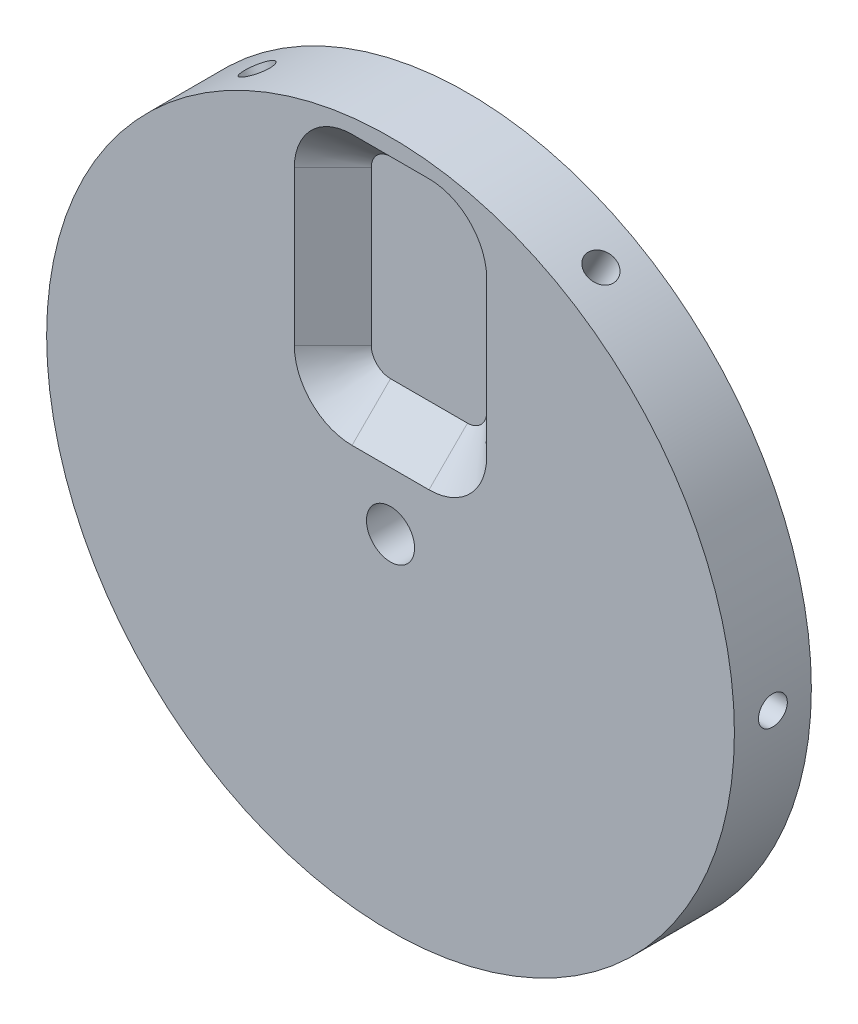
SolidWorks part; units mm, degrees
material "ABS"
ref_plane "Front Plane" through (0, 0, 0) normal (0, 0, 1) x (1, 0, 0)
ref_plane "Top Plane" through (0, 0, 0) normal (0, 1, 0) x (1, 0, 0)
ref_plane "Right Plane" through (0, 0, 0) normal (1, 0, 0) x (0, 0, -1)
sketch "Sketch1" plane through (0, 0, 0) normal (0, 0, 1) x (1, 0, 0)
  circle A0 centre (0, 0) radius 45.4025
  dimension "D1" = 90.805
extrude "Boss-Extrude1" add sketch "Sketch1" along normal blind 10.16
sketch "Sketch2" plane through (0, 0, 0) normal (1, 0, 0) x (0, 0, -1)
  line L0 (-10.16, 0) -> (0, 0) construction
  line L1 (-10.16, 45.4025) -> (-10.16, -45.4025) construction
  circle A0 centre (-5.08, 0) radius 1.905
  point P6 (-5.08, 0)
  dimension "D1" = 3.81
extrude "Cut-Extrude1" cut sketch "Sketch2" along normal blind 7.62 from offset 38.1
ref_axis "Axis1" through (0, 0, 10.16) along (0, 0, -1)
pattern_circular "CirPattern1" count 6 every 60 about axis through (0, 0, 10.16) along (0, 0, -1) of "Cut-Extrude1"
sketch "Sketch3" plane through (0, 0, 0) normal (0, 0, -1) x (-1, 0, 0)
  circle A0 centre (0, 0) radius 3.175
  dimension "D1" = 6.35
extrude "Cut-Extrude2" cut sketch "Sketch3" against normal through all
sketch "Sketch4" plane through (0, 0, 10.16) normal (0, 0, 1) x (1, 0, 0)
  line L1 (-5.08, 38.1) -> (5.08, 38.1)
  line L2 (-7.62, 35.56) -> (-7.62, 15.24)
  line L3 (-5.08, 12.7) -> (5.08, 12.7)
  line L4 (7.62, 35.56) -> (7.62, 15.24)
  arc A0 (-7.62, 15.24) -> (-5.08, 12.7) centre (-5.08, 15.24) ccw
  arc A1 (5.08, 12.7) -> (7.62, 15.24) centre (5.08, 15.24) ccw
  arc A2 (5.08, 38.1) -> (7.62, 35.56) centre (5.08, 35.56) cw
  arc A3 (-5.08, 38.1) -> (-7.62, 35.56) centre (-5.08, 35.56) ccw
  point P6 (0, 12.7)
  point P9 (-7.62, 12.7)
  point P12 (7.62, 12.7)
  point P17 (-7.62, 38.1)
  dimension "D4" = 2.54
  dimension "D1" = 12.7
  dimension "D2" = 25.4
  dimension "D3" = 15.24
extrude "Cut-Extrude3" cut sketch "Sketch4" against normal blind 5.08
chamfer "Chamfer2" distance 5.08 angle 45 8 edges at (0, 12.7, 10.16) (6.8761, 13.4439, 10.16) (-6.8761, 13.4439, 10.16) (7.62, 25.4, 10.16) (-7.62, 25.4, 10.16) (6.8761, 37.3561, 10.16) (-6.8761, 37.3561, 10.16) (0, 38.1, 10.16)
